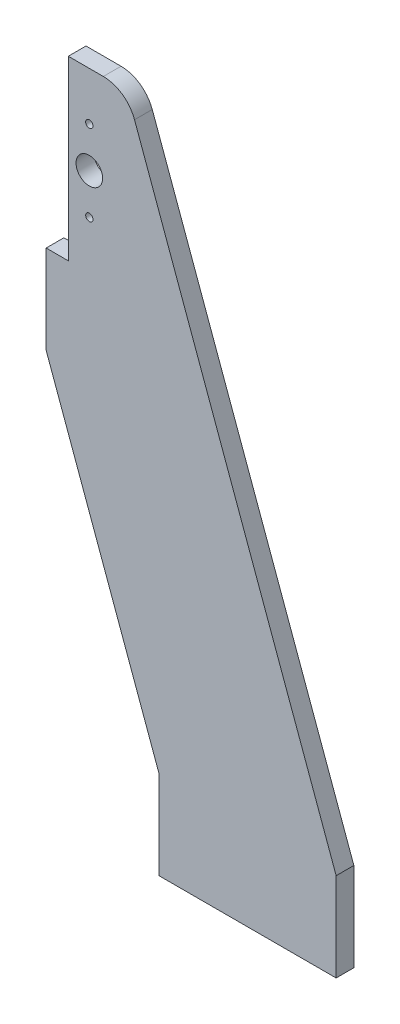
SolidWorks part; units mm, degrees
ref_plane "Alzado" through (0, 0, 0) normal (0, 0, 1) x (1, 0, 0)
ref_plane "Planta" through (0, 0, 0) normal (0, 1, 0) x (1, 0, 0)
ref_plane "Vista lateral" through (0, 0, 0) normal (1, 0, 0) x (0, 0, -1)
sketch "Croquis1" plane through (0, 0, 0) normal (0, 0, 1) x (1, 0, 0)
  line L0 (80, 0) -> (80, 40)
  line L1 (-40.9558, 300) -> (-25.1354, 300)
  line L2 (-50.9558, 220) -> (-50.9558, 180)
  line L3 (0, 0) -> (80, 0)
  line L4 (-11.04, 290.1303) -> (80, 40)
  line L7 (-50.9558, 220) -> (-40.9558, 220)
  line L8 (-40.9558, 300) -> (-40.9558, 220)
  line L9 (-50.9558, 180) -> (0, 40)
  line L11 (0, 40) -> (0, 0)
  arc A2 (-11.04, 290.1303) -> (-25.1354, 300) centre (-25.1354, 285) ccw
  dimension "D7" = 110
  dimension "D9" = 15
  dimension "D1" = 40
  dimension "D2" = 300
  dimension "D3" = 80
  dimension "D4" = 80
  dimension "D5" = 10
  dimension "D6" = 40
  dimension "D8" = 40
  dimension "D10" = 110
extrude "Saliente-Extruir1" add sketch "Croquis1" along normal blind 8
sketch "Croquis2" plane through (0, 0, 0) normal (0, 0, -1) x (-1, 0, 0)
  line L0 (25.1354, 300) -> (40.9558, 300) construction
  line L1 (40.9558, 300) -> (40.9558, 220) construction
  circle A0 centre (31.4558, 260) radius 6
  dimension "D3" = 12
  dimension "D1" = 40
  dimension "D2" = 9.5
extrude "Cortar-Extruir1" cut sketch "Croquis2" against normal through all
hole_wizard "Perforador para roscar para macho de roscar para M42" positions "Croquis3" profile "Croquis4" hole size "M4" standard "DIN"
sketch "Croquis3" plane through (-40.9558, 0, 0) normal (-1, 0, 0) x (0, 0, 1)
  line L0 (3, 220) -> (3, 300)
  line L1 (8, 220) -> (0, 220) construction
  line L2 (8, 300) -> (0, 300) construction
  line L4 (8, 300) -> (8, 220) construction
  line L5 (8, 288) -> (0, 288)
  line L6 (0, 300) -> (0, 220) construction
  line L8 (8, 232) -> (0, 232)
  point P21 (3, 232)
  point P23 (3, 288)
  point P26 (4, 288)
  point P27 (3, 288)
  point P28 (0, 0)
  point P29 (3, 232)
  point P30 (3, 305.2503)
  point P31 (3, 300)
  point P32 (3, 220)
  point P33 (3, 288)
  dimension "D1" = 12
  dimension "D2" = 12
  dimension "D3" = 3
sketch "Croquis4" plane through (-40.9558, 288, 3) normal (0, 1, 0) x (0, 0, 1)
  line L0 (0, 0) -> (0, 10.9914)
  line L1 (0, 10.9914) -> (1.65, 10)
  line L2 (1.65, 10) -> (1.65, 0)
  line L5 (1.65, 0) -> (0, 0)
  line L10 (0, 10.9914) -> (-1.65, 10) construction
  line L11 (0, -6.35) -> (0, 107.95) construction
  dimension "Diámetro de taladro" = 3.3
  dimension "Profundidad de taladro" = 10
  dimension "Ángulo de perforador" = 118
hole_wizard "Taladros de espiga de Ø4.0mm2" positions "Croquis5" profile "Croquis6" hole size "Ø4.0" standard "DIN"
sketch "Croquis5" plane through (-40.9558, 0, 0) normal (-1, 0, 0) x (0, 0, 1)
  line L0 (4, 220) -> (4, 300)
  line L1 (8, 220) -> (0, 220) construction
  line L2 (8, 300) -> (0, 300) construction
  line L4 (8, 300) -> (8, 220) construction
  line L5 (8, 274) -> (0, 274)
  line L6 (0, 300) -> (0, 220) construction
  line L8 (8, 246) -> (0, 246)
  point P21 (4, 274)
  point P23 (4, 246)
  dimension "D1" = 26
  dimension "D2" = 26
sketch "Croquis6" plane through (-40.9558, 246, 4) normal (0, 1, 0) x (0, 0, 1)
  line L0 (0, 0) -> (0, 11.2017)
  line L1 (0, 11.2017) -> (2, 10)
  line L2 (2, 10) -> (2, 0)
  line L5 (2, 0) -> (0, 0)
  line L10 (0, 11.2017) -> (-2, 10) construction
  line L11 (0, -6.35) -> (0, 107.95) construction
  dimension "Diámetro de taladro" = 4
  dimension "Profundidad de taladro" = 10
  dimension "Ángulo de perforador" = 118
hole_wizard "Perforador para roscar para macho de roscar para M44" positions "Croquis7" profile "Croquis8" hole size "M4" standard "DIN"
sketch "Croquis7" plane through (0, 0, 8) normal (0, 0, 1) x (1, 0, 0)
  line L0 (-31.4558, 278.25) -> (-31.4558, 241.75)
  circle A0 centre (-31.4558, 260) radius 6 construction
  point P1 (-31.4558, 278.25)
  point P2 (-31.4558, 241.75)
  dimension "D1" = 18.25
  dimension "D2" = 18.25
sketch "Croquis8" plane through (-31.4558, 278.25, 8) normal (1, 0, 0) x (0, -1, 0)
  line L0 (0, 0) -> (0, 7.9914)
  line L1 (0, 7.9914) -> (1.65, 7)
  line L2 (1.65, 7) -> (1.65, 0)
  line L5 (1.65, 0) -> (0, 0)
  line L10 (0, 7.9914) -> (-1.65, 7) construction
  line L11 (0, -6.35) -> (0, 107.95) construction
  dimension "Diámetro de taladro" = 3.3
  dimension "Profundidad de taladro" = 7
  dimension "Ángulo de perforador" = 118
